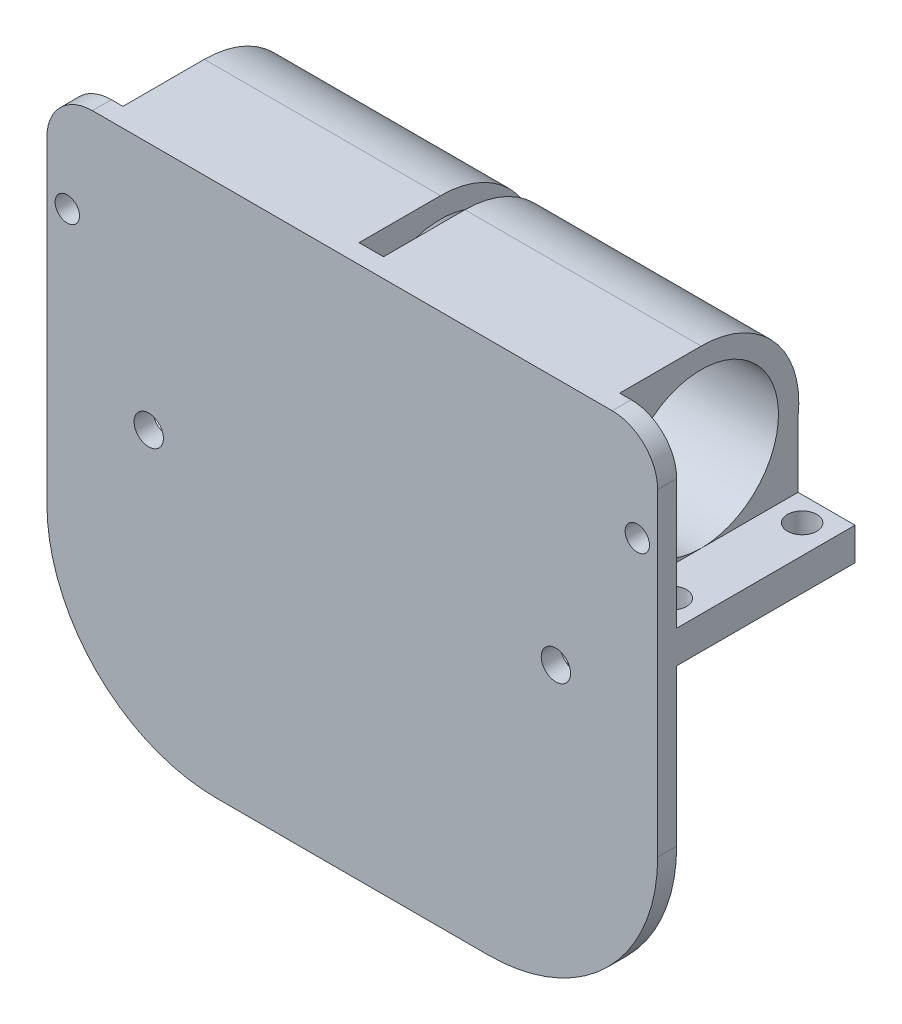
SolidWorks part; units mm, degrees
material "1060 Alloy"
ref_plane "Front Plane" through (0, 0, 0) normal (0, 0, 1) x (1, 0, 0)
ref_plane "Top Plane" through (0, 0, 0) normal (0, 1, 0) x (1, 0, 0)
ref_plane "Right Plane" through (0, 0, 0) normal (1, 0, 0) x (0, 0, -1)
sketch "Sketch1" plane through (0, 0, 0) normal (0, 0, 1) x (1, 0, 0)
  line L0 (-37.5, 0) -> (-25, 0) construction
  line L1 (37.5, -10.5) -> (30, -10.5)
  line L2 (37.5, -10.5) -> (37.5, 10.5)
  line L3 (37.5, 10.5) -> (-37.5, 10.5)
  line L4 (-37.5, -10.5) -> (-37.5, 10.5)
  line L5 (37.5, -10.5) -> (-37.5, 10.5) construction
  line L6 (37.5, 10.5) -> (-37.5, -10.5) construction
  line L7 (-30, -10.5) -> (-37.5, -10.5)
  line L8 (-25, 0) -> (-12.5, 0) construction
  line L9 (-12.5, 0) -> (0, 0) construction
  line L10 (0, 0) -> (12.5, 0) construction
  line L11 (12.5, 0) -> (25, 0) construction
  line L12 (25, 0) -> (37.5, 0) construction
  line L13 (-5, -10.5) -> (-20, -10.5)
  line L14 (20, -10.5) -> (5, -10.5)
  line L15 (-35, 10.5) -> (-35, 8) construction
  line L16 (-35, 8) -> (-37.5, 8) construction
  line L17 (-25, -10.5) -> (-25, 10.5) construction
  line L18 (-12.5, -10.5) -> (-12.5, 10.5) construction
  line L19 (12.5, -10.5) -> (12.5, 10.5) construction
  arc A0 (-20, -10.5) -> (-30, -10.5) centre (-25, -10.5) cw
  arc A1 (5, -10.5) -> (-5, -10.5) centre (0, -10.5) cw
  arc A2 (30, -10.5) -> (20, -10.5) centre (25, -10.5) cw
  circle A3 centre (-25, -10.5) radius 1.7999
  circle A4 centre (0, -10.5) radius 1.7999
  circle A5 centre (25, -10.5) radius 1.7999
  circle A6 centre (-35, 8) radius 1.5
  circle A7 centre (-15, 8) radius 1.5
  circle A8 centre (-10, 8) radius 1.5
  circle A9 centre (10, 8) radius 1.5
  circle A10 centre (35, 8) radius 1.5
  circle A11 centre (15, 8) radius 1.5
  point P0 (0, 0)
  dimension "D4" = 5
  dimension "D5" = 3.5999
  dimension "D7" = 3
  dimension "D1" = 75
  dimension "D2" = 21
  dimension "D3" = 12.5
  dimension "D6" = 2.5
extrude "Boss-Extrude1" add sketch "Sketch1" along normal blind 7
ref_plane "Plane1" through (0, 2.25, 0) normal (0, 1, 0) x (1, 0, 0)
sketch "Sketch2" plane through (0, 2.25, 0) normal (0, 1, 0) x (1, 0, 0)
  line L1 (-37.5, -13.55) -> (-12.5, -13.55) construction
  line L7 (37.5, -7) -> (-37.5, -7)
  line L8 (37.5, -7) -> (37.5, -20.1)
  line L11 (37.5, -20.1) -> (-37.5, -20.1)
  line L12 (-37.5, -7) -> (-37.5, -20.1)
  line L13 (37.5, -7) -> (-37.5, -20.1) construction
  line L14 (37.5, -20.1) -> (-37.5, -7) construction
  line L15 (-12.5, -13.55) -> (12.5, -13.55) construction
  line L16 (12.5, -13.55) -> (37.5, -13.55) construction
  line L17 (12.5, -13.55) -> (12.5, -7) construction
  line L18 (-12.5, -13.55) -> (-12.5, -7) construction
  circle A0 centre (0, -13.55) radius 2.5
  circle A1 centre (6.0001, -13.55) radius 2.6999
  circle A2 centre (-6.0001, -13.55) radius 2.6999
  circle A3 centre (6.0001, -13.55) radius 1.3498
  circle A4 centre (-6.0001, -13.55) radius 1.3498
  circle A5 centre (-18.9999, -13.55) radius 1.3498
  circle A6 centre (-18.9999, -13.55) radius 2.6999
  circle A7 centre (-25, -13.55) radius 2.5
  circle A8 centre (-31.0001, -13.55) radius 1.3498
  circle A9 centre (-31.0001, -13.55) radius 2.6999
  circle A10 centre (31.0001, -13.55) radius 1.3498
  circle A11 centre (31.0001, -13.55) radius 2.6999
  circle A12 centre (25, -13.55) radius 2.5
  circle A13 centre (18.9999, -13.55) radius 1.3498
  circle A14 centre (18.9999, -13.55) radius 2.6999
  point P4 (0, -13.55)
  dimension "D2" = 5
  dimension "D3" = 5.3999
  dimension "D6" = 2.6997
  dimension "D1" = 13.1
  dimension "D4" = 6.0001
  dimension "D5" = 6.0001
  dimension "D7" = 25
extrude "Boss-Extrude2" add sketch "Sketch2" against normal blind 6.988 contours L7 L12 L11 L8 A11 A9 A7 A2 A1 A0 A6 A12 A14 | A9 A8 | A6 A5 | A2 A4 | A1 A3 | A14 A13 | A11 A10 region at (36.7386, 2.25, 13.55) region at (3.3766, 2.25, 13.55) region at (-8.6237, 2.25, 13.55) region at (-21.6234, 2.25, 13.55) region at (-33.6237, 2.25, 13.55) region at (28.3766, 2.25, 13.55) region at (16.3763, 2.25, 13.55)
extrude "Cut-Extrude1" cut sketch "Sketch2<3>" against normal blind 2.5 contours A9 A8 | A6 A5 | A2 A4 | A1 A3 | A14 A13 | A11 A10 region at (3.3766, 2.25, 13.55) region at (-8.6237, 2.25, 13.55) region at (-21.6234, 2.25, 13.55) region at (-33.6237, 2.25, 13.55) region at (28.3766, 2.25, 13.55) region at (16.3763, 2.25, 13.55)
sketch "Sketch2<3>" plane through (0, 2.25, 0) normal (0, 1, 0) x (1, 0, 0) same geometry as "Sketch2"
ref_plane "Plane2" through (-37.5, -4.738, 7) normal (-1, 0, 0) x (0, 0, 1)
sketch "Sketch5" plane through (0, 2.25, 0) normal (0, 1, 0) x (1, 0, 0)
  line L1 (-37.5, -7) -> (37.5, -7)
  line L2 (-37.5, -7) -> (-37.5, -20.1)
  line L3 (-37.5, -20.1) -> (37.5, -20.1)
  line L4 (37.5, -7) -> (37.5, -20.1)
  line L5 (-37.5, -7) -> (37.5, -20.1) construction
  line L6 (-37.5, -20.1) -> (37.5, -7) construction
  point P4 (0, -13.55)
extrude "Cut-Extrude3" cut sketch "Sketch5" against normal blind 21.082
sketch "Sketch6" plane through (0, 10.5, 0) normal (0, 1, 0) x (1, 0, 0)
  line L4 (37.5, 0) -> (-37.5, 0)
  line L5 (-37.5, 0) -> (-37.5, -7)
  line L6 (-37.5, -7) -> (37.5, -7)
  line L7 (37.5, -7) -> (37.5, 0)
  line L8 (37.5, 0) -> (-37.5, 0)
  line L9 (-37.5, 0) -> (-37.5, -7)
  line L10 (-37.5, -7) -> (37.5, -7)
  line L11 (37.5, -7) -> (37.5, 0)
  dimension "D1" = 0
extrude "Boss-Extrude3" add sketch "Sketch6" along normal blind 9.5
sketch "Sketch8" plane through (0, 0, 0) normal (0, 0, -1) x (-1, 0, 0)
  line L6 (-37.5, 20) -> (37.5, 20)
  line L8 (-37.5, 20) -> (-37.5, -18.0302)
  line L9 (-37.5, -18.0302) -> (37.5, -18.0302)
  line L10 (37.5, 20) -> (37.5, -18.0302)
  line L11 (-37.5, 20) -> (37.5, -18.0302) construction
  line L12 (-37.5, -18.0302) -> (37.5, 20) construction
  point P4 (0, 0.9849)
extrude "Cut-Extrude4" cut sketch "Sketch8" against normal blind 4.666
ref_plane "Plane4" through (0, -45.5, 0) normal (0, -1, 0) x (-1, 0, 0)
sketch "Sketch10" plane through (0, -45.5, 0) normal (0, -1, 0) x (-1, 0, 0)
  line L1 (-37.5, -7) -> (37.5, -7)
  line L2 (-37.5, -7) -> (-37.5, -4.666)
  line L3 (-37.5, -4.666) -> (37.5, -4.666)
  line L4 (37.5, -7) -> (37.5, -4.666)
  line L5 (-37.5, -7) -> (37.5, -4.666) construction
  line L6 (-37.5, -4.666) -> (37.5, -7) construction
  point P4 (0, -5.833)
extrude "Boss-Extrude5" add sketch "Sketch10" against normal up to surface (35 mm away) up to face at (12.5, -10.5, 5.833)
sketch "Sketch11" plane through (0, 0, 4.666) normal (0, 0, -1) x (-1, 0, 0)
  circle A0 centre (-25, -10.5) radius 1.7999
  circle A1 centre (0, -10.5) radius 1.7999
  circle A2 centre (25, -10.5) radius 1.7999
extrude "Cut-Extrude5" cut sketch "Sketch11" against normal blind 5
sketch "Sketch15" plane through (0, 0, 7) normal (0, 0, 1) x (1, 0, 0)
  line L1 (-20.5223, 1.9953) -> (24.1312, 1.9953)
  line L2 (-20.5223, 1.9953) -> (-20.5223, 15.6126)
  line L3 (-20.5223, 15.6126) -> (24.1312, 15.6126)
  line L4 (24.1312, 1.9953) -> (24.1312, 15.6126)
  line L5 (-20.5223, 1.9953) -> (24.1312, 15.6126) construction
  line L6 (-20.5223, 15.6126) -> (24.1312, 1.9953) construction
  line L7 (-7.3653, -8.2939) -> (4.3629, -8.2939)
  line L8 (-7.3653, -8.2939) -> (-7.3653, -14.2814)
  line L9 (-7.3653, -14.2814) -> (4.3629, -14.2814)
  line L10 (4.3629, -8.2939) -> (4.3629, -14.2814)
  line L11 (-7.3653, -8.2939) -> (4.3629, -14.2814) construction
  line L12 (-7.3653, -14.2814) -> (4.3629, -8.2939) construction
  point P4 (1.8044, 8.8039)
  point P9 (-1.5012, -11.2877)
extrude "Boss-Extrude7" add sketch "Sketch15" against normal up to surface (2.334 mm away) up to face at (23.2001, -10.5, 4.666)
ref_plane "Plane5" through (30.5, 0, 0) normal (1, 0, 0) x (0, 0, -1)
sketch "Sketch16" plane through (30.5, 0, 0) normal (1, 0, 0) x (0, 0, -1)
  line L0 (-4.666, 6.5) -> (-4.666, 9.5) construction
  line L1 (-4.666, 6.5) -> (-4.666, 9.5)
  line L2 (-4.666, 20) -> (-4.666, -45.5) construction
  line L3 (5.334, 20) -> (-4.666, 20)
  line L4 (5.334, -4) -> (-4.666, -4)
  line L5 (-4.666, 20) -> (-4.666, -4)
  line L6 (5.334, -1.5) -> (5.334, -4)
  line L7 (17.2399, 6.5) -> (17.2399, -4)
  line L8 (17.2399, -4) -> (5.334, -4)
  circle A0 centre (5.334, 8) radius 9.5
  arc A1 (5.334, -4) -> (5.334, 20) centre (5.334, 8) ccw
  circle A3 centre (5.334, 8) radius 12 construction
  point P5 (-4.666, 8)
  point P13 (16.834, 8)
  dimension "D1" = 19
  dimension "D3" = 10
  dimension "D2" = 2.5
extrude "Boss-Extrude9" add sketch "Sketch16" against normal blind 29 separate body contours L4 A1 L3 L5 L1 A0 | A1 L8 L7 region at (30.5, 8, 4.3404) region at (30.5, -1.4175, -14.5623)
mirror "Mirror1" about plane through (0, 0, 0) normal (1, 0, 0) of bodies 114
combine bodies "Combine1" operation type add bodies to combine 115 114 113
sketch "Sketch17" plane through (0, 0, 0) normal (1, 0, 0) x (0, 0, -1)
  line L0 (-4.666, -45.5) -> (-7, -45.5) construction
  line L1 (5.334, -45.5) -> (-4.666, -45.5)
  line L3 (5.334, -21.5) -> (-4.666, -21.5)
  line L4 (-4.666, 20) -> (-4.666, -45.5) construction
  line L5 (-4.666, -21.5) -> (-4.666, -45.5)
  circle A2 centre (5.334, 8) radius 9.5 construction
  circle A3 centre (5.334, 8) radius 9.5 construction
  circle A5 centre (5.334, -33.5) radius 9.5
  arc A6 (5.334, -45.5) -> (5.334, -21.5) centre (5.334, -33.5) ccw
  circle A8 centre (5.334, -33.5) radius 12 construction
  point P2 (16.8097, -12.4915)
  point P3 (5.334, -16)
  point P13 (16.8097, -19.9915)
  dimension "D1" = 19
  dimension "D2" = 2.5
extrude "Boss-Extrude11" add sketch "Sketch17" along normal mid plane 29
sketch "Sketch18" plane through (0, 0, 4.666) normal (0, 0, -1) x (-1, 0, 0)
  line L0 (-14.5, -21.5) -> (-14.5, -45.5) construction
  line L1 (-14.5, -24) -> (-14.5, -43) construction
  line L2 (-14.5, -21.5) -> (-14.5, -45.5)
  line L3 (-14.5, -24) -> (-14.5, -43)
  line L4 (-30.5, 20) -> (-30.5, -4) construction
  line L5 (-30.5, 20) -> (-30.5, -4)
  line L6 (-30.5, -4) -> (-37.5, -4)
  line L7 (-37.5, 20) -> (-37.5, -45.5) construction
  line L8 (-37.5, -4) -> (-37.5, -6)
  line L9 (-37.5, -6) -> (-21.77, -6)
  line L10 (-1.5, -4) -> (-30.5, -4) construction
  line L11 (-21.77, -6) -> (-21.77, -7.0074)
  line L12 (-37.5, -7) -> (-22.77, -7)
  line L13 (-22.77, -7) -> (-22.77, -7.0074)
  line L14 (-18.7626, -4) -> (-16.114, -4)
  line L15 (-37.5, -3) -> (-30.5, -3)
  line L16 (-37.5, -3) -> (-37.5, -4)
  circle A1 centre (-18.7626, -7.0074) radius 1.5
  arc A2 (-18.7626, -4) -> (-21.77, -7.0074) centre (-18.7626, -7.0074) cw
  arc A3 (-16.114, -4) -> (-22.77, -7.0074) centre (-18.7626, -7.0074) cw
  arc A5 (-18.7626, -3) -> (-22.77, -7.0074) centre (-18.7626, -7.0074) cw construction
  line M15 (-1.5, -4) -> (-30.5, -4)
  line M16 (-30.5, -4) -> (-30.5, 20)
  line M18 (-37.5, 20) -> (-37.5, -45.5)
  dimension "D2" = 3
  dimension "D3" = 1
  dimension "D1" = 2
  dimension "D4" = 1
extrude "Boss-Extrude12" [suppressed] add sketch "Sketch18" along normal blind 6 separate body contours L15 L6 M18 M16 | A3 A2 L11 L9 L12 L13 M15 M18 | A1
mirror "Mirror2" [suppressed] about plane through (0, 0, 0) normal (1, 0, 0) of bodies 121 119 120
combine bodies "Combine2" [suppressed] operation type add bodies to combine 122 124 120 119 121 118 123
fillet "Fillet5" radius 20.828 2 edges at (-37.5, -45.5, 5.833) (37.5, -45.5, 5.833)
fillet "Fillet6" radius 5.588 2 edges at (-37.5, 20, 5.833) (37.5, 20, 5.833)
fillet "Fillet7" [suppressed] radius 0.508
fillet "Fillet8" [suppressed] radius 3.048
sketch "Sketch20" plane through (0, 0, 4.666) normal (0, 0, -1) x (-1, 0, 0)
  line L0 (-37.5, 14.412) -> (-37.5, -24.672) construction
  line L1 (-37.5, -1.5) -> (37.5, -1.5)
  line L2 (-37.5, -1.5) -> (-37.5, -5.5)
  line L5 (37.5, -24.672) -> (37.5, 14.412) construction
  line L6 (1.5, -4) -> (30.5, -4) construction
  line L7 (0, -5.5) -> (0, -7.5) construction
  line L8 (37.5, -5.5) -> (0, -5.5) construction
  line L9 (37.5, -1.5) -> (37.5, -5.5)
  arc A0 (-37.5, -5.5) -> (37.5, -5.5) centre (0, 345.0625) ccw
  dimension "D1" = 4
  dimension "D2" = 2.5
  dimension "D3" = 2
extrude "Boss-Extrude13" add sketch "Sketch20" along normal up to surface (21.9059 mm away) up to face at (16, 1.25, -17.2399)
sketch "Sketch21" plane through (0, -1.5, 0) normal (0, 1, 0) x (1, 0, 0)
  line L1 (34, 14.2399) -> (34, -1.7601) construction
  line L3 (37.5, 17.2399) -> (30.5, 17.2399) construction
  line L4 (0, 0) -> (0, 6.6842) construction
  line L5 (-34, 14.2399) -> (-34, -1.7601) construction
  circle A1 centre (34, 14.2399) radius 1.8
  circle A2 centre (34, -1.7601) radius 1.8
  circle A3 centre (-34, -1.7601) radius 1.8
  circle A4 centre (-34, 14.2399) radius 1.8
  dimension "D1" = 3.6
  dimension "D2" = 3.6
  dimension "D3" = 16
  dimension "D4" = 3
  dimension "D5" = 34
extrude "Cut-Extrude6" cut sketch "Sketch21" against normal up to next
